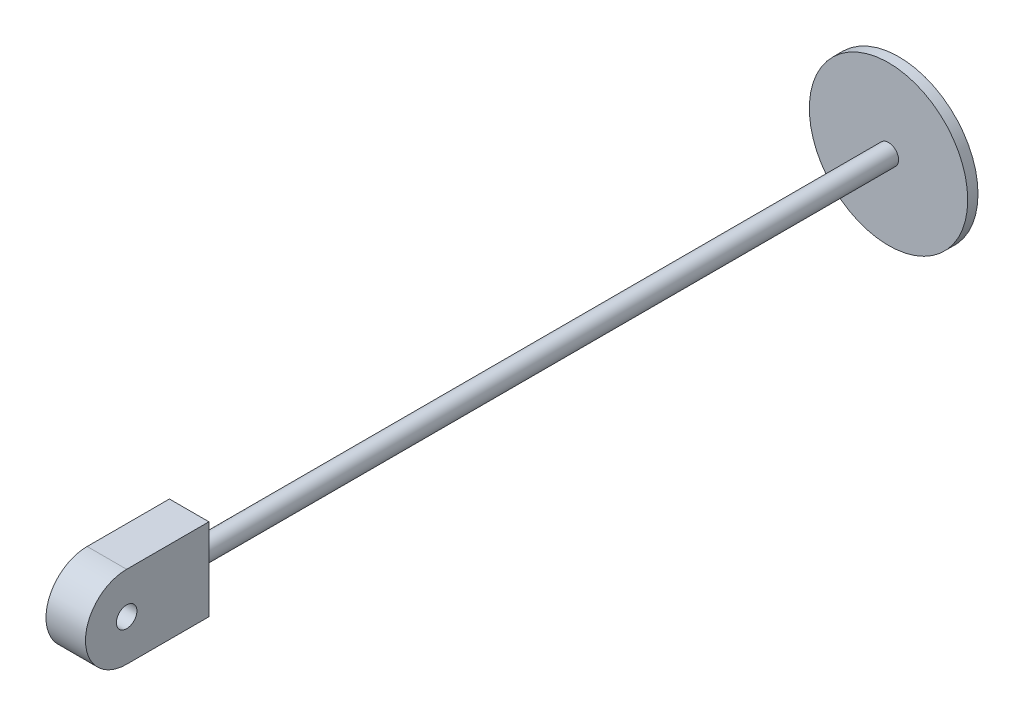
SolidWorks part; units mm, degrees
ref_plane "Front Plane" through (0, 0, 0) normal (0, 0, 1) x (1, 0, 0)
ref_plane "Top Plane" through (0, 0, 0) normal (0, 1, 0) x (1, 0, 0)
ref_plane "Right Plane" through (0, 0, 0) normal (1, 0, 0) x (0, 0, -1)
sketch "Sketch1" plane through (0, 0, 0) normal (0, 0, 1) x (1, 0, 0)
  circle A0 centre (0, 0) radius 9.625
  dimension "D1" = 19.25
extrude "Boss-Extrude1" add sketch "Sketch1" along normal mid plane 1.25
sketch "Sketch2" plane through (0, 0, 0.625) normal (0, 0, 1) x (1, 0, 0)
  circle A0 centre (0, 0) radius 1.225
  dimension "D1" = 2.45
extrude "Boss-Extrude2" add sketch "Sketch2" along normal blind 85
sketch "Sketch3" plane through (0, 0, 0) normal (1, 0, 0) x (0, 0, -1)
  line L0 (-85.625, 5) -> (-85.625, -5)
  line L1 (-85.625, 1.225) -> (-85.625, -1.225) construction
  line L2 (-85.625, 5) -> (-95.625, 5)
  line L4 (-95.625, -5) -> (-85.625, -5)
  arc A0 (-95.625, 5) -> (-95.625, -5) centre (-95.625, 0) ccw
  point P4 (-85.625, 0)
  dimension "D3" = 5
  dimension "D1" = 10
  dimension "D2" = 10
extrude "Boss-Extrude3" add sketch "Sketch3" along normal mid plane 4.8
sketch "Sketch4" plane through (-2.4, 0, 0) normal (-1, 0, 0) x (0, 0, 1)
  circle A0 centre (95.625, 0) radius 1.25
  arc A1 (95.625, -5) -> (95.625, 5) centre (95.625, 0) ccw construction
  dimension "D1" = 2.5
extrude "Cut-Extrude1" cut sketch "Sketch4" against normal blind 10
ref_axis "Axis2" [suppressed] through (2.4, 0, 55.625) along (-1, 0, 0)
ref_point "Point2" [suppressed]
ref_axis "Axis1" through (2.4, 0, 95.625) along (-1, 0, 0)
ref_point "Point1"
